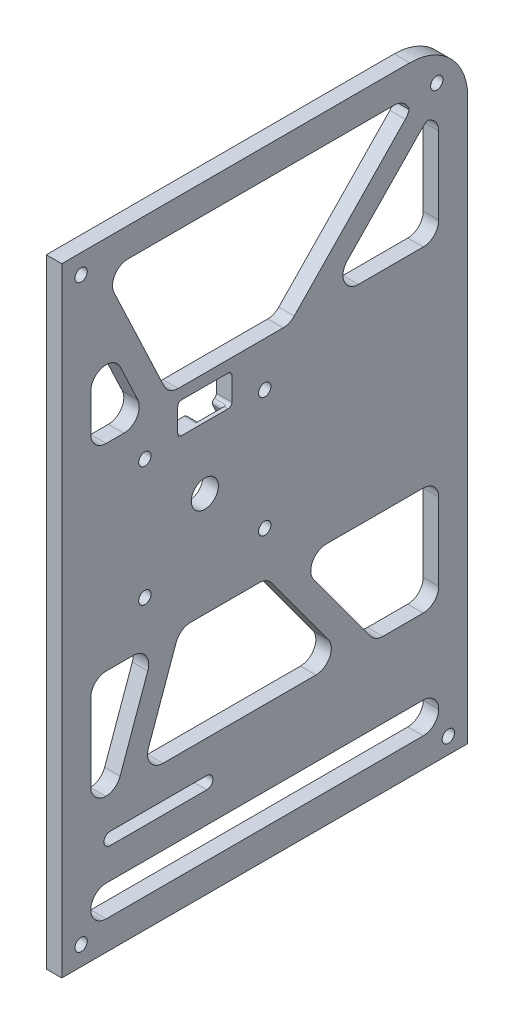
SolidWorks part; units mm, degrees
ref_plane "Front Plane" through (0, 0, 0) normal (0, 0, 1) x (1, 0, 0)
ref_plane "Top Plane" through (0, 0, 0) normal (0, 1, 0) x (1, 0, 0)
ref_plane "Right Plane" through (0, 0, 0) normal (1, 0, 0) x (0, 0, -1)
sketch "Sketch2" plane through (0, 0, 0) normal (1, 0, 0) x (0, 0, -1)
  line L1 (0, 0) -> (105, 0)
  line L2 (0, 0) -> (0, 160)
  line L3 (0, 160) -> (90, 160)
  line L4 (105, 0) -> (105, 145)
  line L5 (10.8174, 152.5) -> (90, 152.5)
  line L8 (90, 145) -> (105, 160) construction
  line L9 (90, 145) -> (105, 145) construction
  line L11 (7.5, 152.5) -> (90, 152.5) construction
  line L12 (7.5, 7.5) -> (7.5, 152.5) construction
  line L13 (7.5, 7.5) -> (97.5, 7.5) construction
  line L14 (97.5, 7.5) -> (97.5, 145) construction
  line L17 (12.5, 25) -> (37.5, 25) construction
  line L22 (12.5, 26.6) -> (37.5, 26.6)
  line L23 (12.5, 23.4) -> (37.5, 23.4)
  line L24 (7.5, 35) -> (7.5, 63)
  line L25 (97.5, 35) -> (97.5, 63)
  line L35 (37, 121.859) -> (37, 90) construction
  line L36 (37, 90) -> (7.5, 152.5) construction
  line L44 (44, 106) -> (30, 106)
  line L49 (44, 106) -> (44, 114)
  line L50 (44, 114) -> (30, 114)
  line L51 (30, 106) -> (30, 114)
  line L52 (44, 106) -> (30, 114) construction
  line L53 (44, 114) -> (30, 106) construction
  line L62 (58.9543, 117) -> (27.5734, 117)
  line L97 (37, 90) -> (7.5, 7.5) construction
  line L98 (24.1594, 63) -> (14.1473, 35)
  line L99 (7.5, 145.4716) -> (7.5, 114)
  line L100 (97, 152) -> (37, 90) construction
  line L102 (90, 152.5) -> (90, 149.0806)
  line L103 (90, 160) -> (105, 160) construction
  line L104 (105, 160) -> (105, 145) construction
  line L106 (97.5, 145) -> (97.5, 117)
  line L107 (94.4006, 145) -> (67.3038, 117)
  line L108 (94.4006, 145) -> (97.5, 145)
  line L109 (90, 149.0806) -> (58.9543, 117)
  line L110 (67.3038, 117) -> (97.5, 117)
  line L115 (97.5, 7.5) -> (7.5, 7.5)
  line L118 (97.5, 35) -> (81.0535, 35)
  line L119 (97.5, 63) -> (60.5202, 63)
  line L120 (30.5315, 63) -> (20.5194, 35)
  line L121 (24.1594, 63) -> (7.5, 63)
  line L122 (37, 90) -> (97.5, 7.5) construction
  line L123 (22.3546, 114) -> (7.5, 114)
  line L124 (53.0798, 63) -> (73.6131, 35)
  line L125 (34.1752, 91.0101) -> (4.6752, 8.5101) construction
  line L126 (27.5734, 117) -> (10.8174, 152.5)
  line L127 (22.3546, 114) -> (7.5, 145.4716)
  line L128 (53.0798, 63) -> (30.5315, 63)
  line L129 (39.8248, 88.9899) -> (10.3248, 6.4899) construction
  line L130 (14.1473, 35) -> (7.5, 35)
  line L133 (7.5, 15.5) -> (97.5, 15.5)
  line L134 (60.5202, 63) -> (81.0535, 35)
  line L135 (34.5808, 88.2259) -> (95.0808, 5.7259) construction
  line L136 (73.6131, 35) -> (20.5194, 35)
  line L140 (7.5, 15.5) -> (7.5, 7.5)
  line L141 (97.5, 15.5) -> (97.5, 7.5)
  arc A0 (90, 160) -> (105, 145) centre (90, 145) cw
  circle A11 centre (97, 152) radius 1.6
  arc A16 (12.5, 26.6) -> (12.5, 23.4) centre (12.5, 25) ccw
  arc A17 (37.5, 23.4) -> (37.5, 26.6) centre (37.5, 25) ccw
  circle A19 centre (52.5, 105.5) radius 1.6
  circle A22 centre (37, 90) radius 3.5
  circle A24 centre (52.5, 74.5) radius 1.6
  circle A25 centre (21.5, 74.5) radius 1.6
  circle A26 centre (21.5, 105.5) radius 1.6
  arc A28 (90, 152.5) -> (97.5, 145) centre (90, 145) cw construction
  circle A29 centre (5, 5) radius 1.6
  circle A30 centre (100, 4.1732) radius 1.6
  circle A31 centre (5, 155) radius 1.6
  point P27 (95.2179, 153.7533)
  point P28 (34.2179, 91.7533)
  point P34 (25, 25)
  point P43 (98.7821, 150.2467)
  point P47 (37.7821, 88.2467)
  point P52 (37, 110)
  point P53 (46.5, 99)
  point P58 (46.5, 115)
  point P59 (25.5, 115)
  point P60 (25.5, 99)
  point P66 (37.9972, 91.5038)
  point P67 (37, 90)
  point P75 (38.2565, 91.0762)
  point P76 (7.2565, 156.0762)
  point P77 (33.7435, 88.9238)
  point P78 (2.7435, 153.9238)
  point P85 (101.9972, 6.5038)
  dimension "D1" = 15
  dimension "D6" = 3.2
  dimension "D7" = 5
  dimension "D8" = 8
  dimension "D9" = 5
  dimension "D10" = 4.1732
  dimension "D11" = 8
  dimension "D12" = 7.5
  dimension "D13" = 6
  dimension "D14" = 3.2
  dimension "D15" = 25
  dimension "D19" = 5
  dimension "D20" = 37
  dimension "D21" = 3.2
  dimension "D22" = 70
  dimension "D23" = 15.5
  dimension "D34" = 7
  dimension "D36" = 7.5
  dimension "D2" = 160
  dimension "D3" = 105
  dimension "D5" = 45
  dimension "D16" = 7.5
  dimension "D17" = 10
  dimension "D18" = 25
  dimension "D24" = 15.5
  dimension "D25" = 20
  dimension "D26" = 3
  dimension "D27" = 3
  dimension "D28" = 4
  dimension "D29" = 31
  dimension "D31" = 8
  dimension "D30" = 14
  dimension "D33" = 31
  dimension "D35" = 3
  dimension "D32" = 3
  dimension "D37" = 27
  dimension "D38" = 7.5
  dimension "D39" = 7.5
  dimension "D40" = 5
  dimension "D41" = 5
  dimension "D42" = 5
  dimension "D43" = 7.5
  dimension "D46" = 3
  dimension "D48" = 3
  dimension "D49" = 12.5
  dimension "D4" = 7.5
  dimension "D44" = 3
  dimension "D45" = 3
  dimension "D47" = 3
extrude "Boss-Extrude1" add sketch "Sketch2" along normal blind 4
chamfer "Chamfer1" distance 1.5 angle 45 8 edges at (0, 105.5, -54.1) (0, 155, -6.6) (0, 152, -98.6) (0, 74.5, -54.1) (0, 74.5, -23.1) (0, 105.5, -23.1) (0, 4.1732, -101.6) (0, 5, -6.6)
fillet "Fillet2" radius 1 4 edges at (2, 114, -44) (2, 106, -44) (2, 106, -30) (2, 114, -30)
fillet "Fillet3" radius 4 28 edges at (2, 152.5, -90) (2, 145, -97.5) (2, 117, -97.5) (2, 117, -67.3038) (2, 145, -94.4006) (2, 149.0806, -90) (2, 117, -27.5734) (2, 145.4716, -7.5) (2, 114, -7.5) (2, 114, -22.3546) (2, 63, -7.5) (2, 63, -24.1594) (2, 35, -14.1473) (2, 35, -7.5) (2, 35, -20.5194) (2, 35, -73.6131) (2, 35, -97.5) (2, 35, -81.0535) (2, 63, -97.5) (2, 63, -30.5315) (2, 63, -53.0798) (2, 63, -60.5202) (2, 117, -58.9543) (2, 152.5, -10.8174) (2, 7.5, -7.5) (2, 15.5, -7.5) (2, 7.5, -97.5) (2, 15.5, -97.5)
sketch "Sketch3" plane through (0, 0, 0) normal (-1, 0, 0) x (0, 0, 1)
  line L0 (-105, 95.5) -> (-52.5, 95.5) construction
  line L1 (-105, 0) -> (-105, 145) construction
  line L4 (-39.5, 106) -> (-38.9808, 107.9314) construction
  line L5 (-52.5, 95.5) -> (-42.3226, 95.5) construction
  line L6 (-37, 121.859) -> (-37, 90) construction
  line L7 (-44, 106) -> (-30, 106) construction
  line L8 (-105, 92.5) -> (-52.5, 92.5)
  line L9 (-36.6029, 105.2212) -> (-36.0837, 107.1526)
  line L10 (-105, 98.5) -> (-52.5, 98.5)
  line L11 (-42.3971, 106.7788) -> (-41.8779, 108.7102)
  line L12 (-52.5, 105.5) -> (-52.5, 74.5) construction
  line L13 (-105, 92.5) -> (-105, 98.5)
  line L14 (-36.0837, 107.1526) -> (-41.8779, 108.7102)
  line L17 (-42.3226, 95.5) -> (-39.5, 106) construction
  line L19 (-97, 152) -> (-37, 90) construction
  spline S0 degree 2 poles (-52.5, 95.5) (-42.3226, 95.5) (-39.5, 106) knots 0 0 0 1 1 1 construction
  spline S1 degree 1 poles (-52.5, 92.5) (-36.6029, 105.2212) knots 0 0 1 1 construction
  spline S2 degree 3 poles (-52.5, 92.5) (-52.0179, 92.5) (-51.0448, 92.5315) (-49.1758, 92.7252) (-46.9363, 93.2222) (-44.4522, 94.2535) (-42.2241, 95.7235) (-40.3092, 97.5997) (-38.7341, 99.8266) (-37.6975, 101.9403) (-37.0242, 103.7646) (-36.7331, 104.7367) (-36.6029, 105.2212) knots 0 0 0 0 0.0625 0.125 0.25 0.375 0.5 0.625 0.75 0.875 0.9375 1 1 1 1
  spline S3 degree 1 poles (-52.5, 98.5) (-42.3971, 106.7788) knots 0 0 1 1 construction
  spline S4 degree 3 poles (-52.5, 98.5) (-52.1527, 98.5) (-51.4407, 98.5232) (-50.1604, 98.6576) (-48.7274, 98.9809) (-47.274, 99.5903) (-46.0218, 100.417) (-44.9165, 101.4946) (-43.9317, 102.8748) (-43.2157, 104.3229) (-42.7222, 105.6559) (-42.4966, 106.4087) (-42.3971, 106.7788) knots 0 0 0 0 0.0625 0.125 0.25 0.375 0.5 0.625 0.75 0.875 0.9375 1 1 1 1
  dimension "D4" = 2
  dimension "D1" = 3
  dimension "D3" = 10
  dimension "D6" = 2.5
  dimension "D2" = 3
extrude "Cut-Extrude1" cut sketch "Sketch3" against normal blind 3
sketch "Sketch4" plane through (0, 0, 0) normal (-1, 0, 0) x (0, 0, 1)
  line L1 (-82.5, 98.5) -> (-77.5, 98.5)
  line L2 (-82.5, 98.5) -> (-82.5, 95.5)
  line L3 (-82.5, 95.5) -> (-77.5, 95.5)
  line L4 (-77.5, 98.5) -> (-77.5, 95.5)
  line L6 (-105, 92.5) -> (-100, 92.5)
  line L7 (-105, 92.5) -> (-105, 95.5)
  line L8 (-105, 95.5) -> (-100, 95.5)
  line L9 (-100, 92.5) -> (-100, 95.5)
  line L10 (-55, 92.5) -> (-60, 92.5)
  line L11 (-55, 92.5) -> (-55, 95.5)
  line L12 (-55, 95.5) -> (-60, 95.5)
  line L13 (-60, 92.5) -> (-60, 95.5)
  line L14 (-52.5, 98.5) -> (-105, 98.5) construction
  line L17 (-105, 92.5) -> (-52.5, 92.5) construction
  dimension "D1" = 5
  dimension "D2" = 5
  dimension "D3" = 5
  dimension "D4" = 3
  dimension "D5" = 3
  dimension "D6" = 3
  dimension "D7" = 17.5
  dimension "D8" = 17.5
extrude "Boss-Extrude2" add sketch "Sketch4" against normal blind 1
chamfer "Chamfer2" distance 1.75 angle 30 3 edges at (1, 92.5, -57.5) (1, 98.5, -80) (1, 92.5, -102.5) first distance on face at (1, 94, -57.5) first distance on face at (1, 97, -80) first distance on face at (1, 94, -102.5)
fillet "Fillet4" radius 1 8 edges at (0.5, 95.5, -55) (0.5, 95.5, -100) (0.5, 95.5, -60) (0.5, 95.5, -77.5) (0.5, 95.5, -82.5) (0.5, 95.5, -105) (1.5, 106, -36.3935) (1.5, 106, -42.6235)
